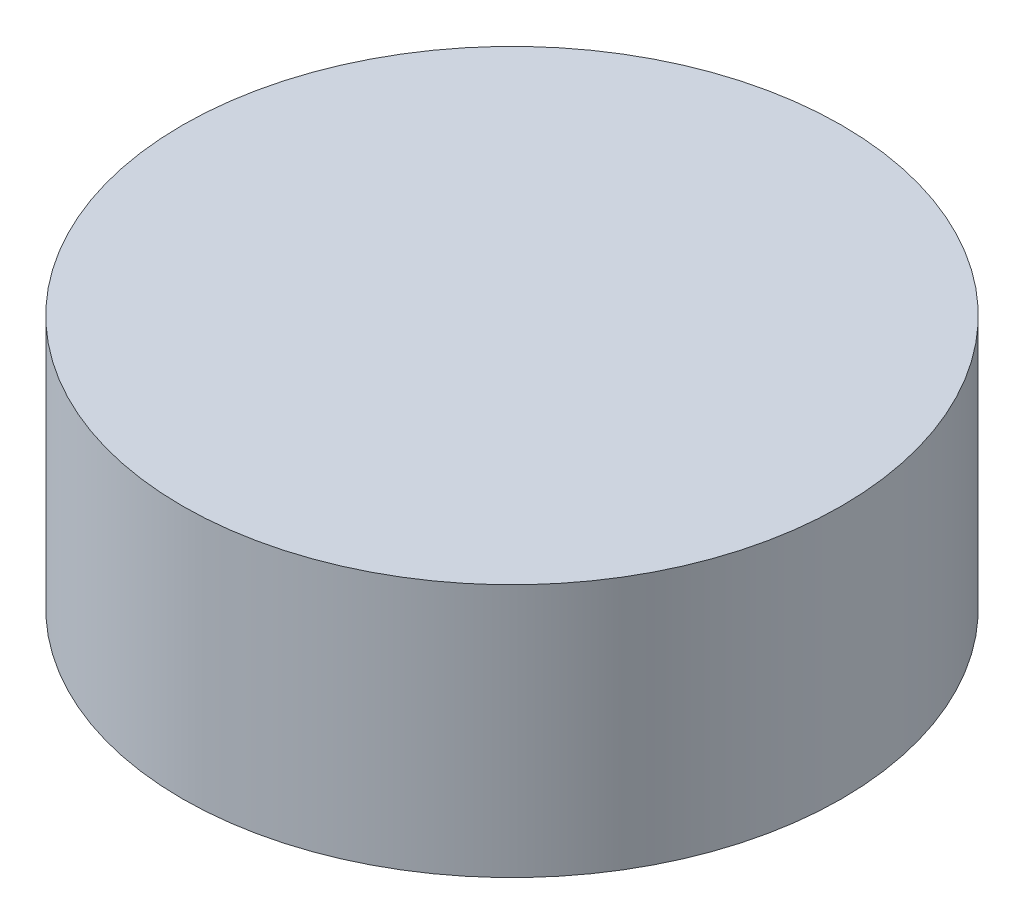
SolidWorks part; units mm, degrees
ref_plane "Спереди" through (0, 0, 0) normal (0, 0, 1) x (1, 0, 0)
ref_plane "Сверху" through (0, 0, 0) normal (0, 1, 0) x (1, 0, 0)
ref_plane "Справа" through (0, 0, 0) normal (1, 0, 0) x (0, 0, -1)
sketch "Эскиз1" plane through (0, 0, 0) normal (0, 1, 0) x (1, 0, 0)
  circle A0 centre (0, 0) radius 32.5
extrude "abot_right_wheel" add sketch "Эскиз1" along normal blind 25
ref_axis "AXIS_RIGHT_WHEEL" through (0, 25, 0) along (0, -1, 0)
